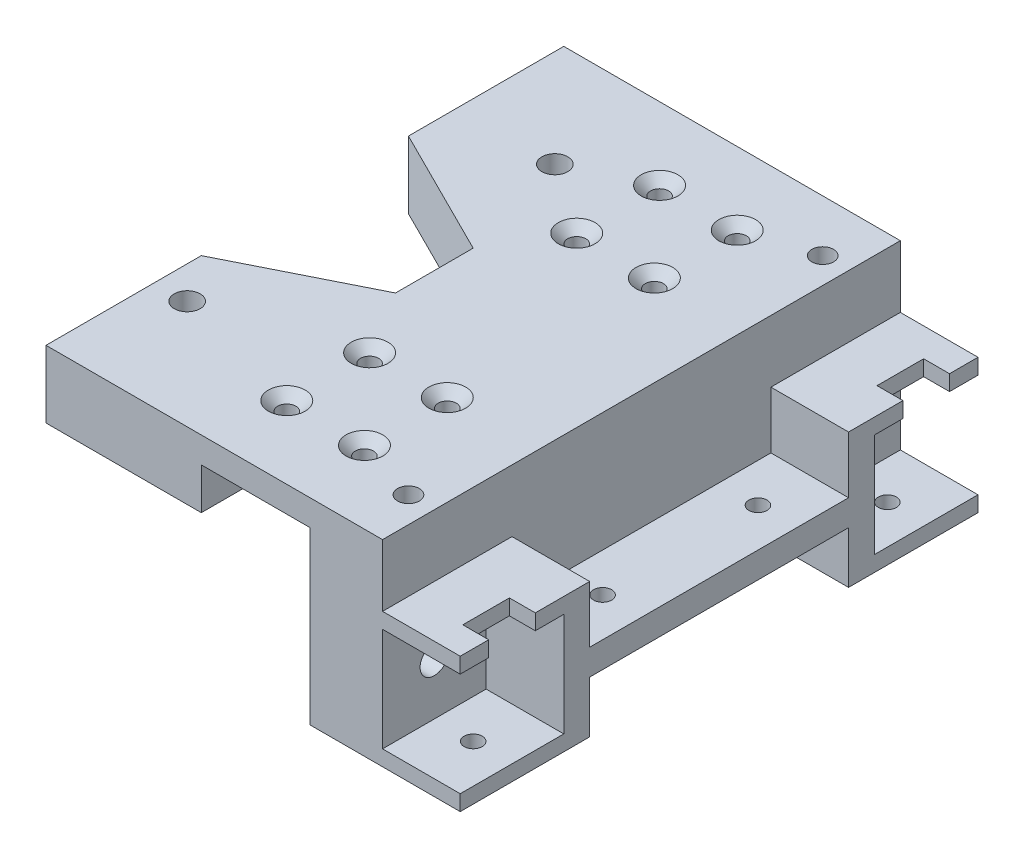
SolidWorks part; units mm, degrees
ref_plane "Front Plane" through (0, 0, 0) normal (0, 0, 1) x (1, 0, 0)
ref_plane "Top Plane" through (0, 0, 0) normal (0, 1, 0) x (1, 0, 0)
ref_plane "Right Plane" through (0, 0, 0) normal (1, 0, 0) x (0, 0, -1)
sketch "Sketch1" plane through (0, 0, 0) normal (0, 1, 0) x (1, 0, 0)
  line L0 (0, 50) -> (0, -50) construction
  line L1 (-10, 50) -> (10, 50)
  line L2 (-10, 50) -> (-10, -50)
  line L3 (-10, -50) -> (10, -50)
  line L4 (10, 50) -> (10, -50) construction
  line L5 (-10, 50) -> (10, -50) construction
  line L6 (-10, -50) -> (10, 50) construction
  line L7 (-7.5, 36) -> (7.5, 36) construction
  line L8 (-7.5, 36) -> (7.5, 20) construction
  line L9 (-10, 0) -> (10, 0) construction
  line L10 (-7.5, -36) -> (7.5, -20) construction
  line L11 (-7.5, -36) -> (7.5, -36) construction
  line L12 (-7.5, 20) -> (7.5, 20) construction
  line L13 (10, 50) -> (11, 50)
  line L14 (11, 50) -> (11, -50)
  line L15 (11, -50) -> (10, -50)
  circle A0 centre (-7.5, 36) radius 1.75
  circle A1 centre (7.5, 36) radius 1.75
  circle A2 centre (-7.5, 20) radius 1.75
  circle A3 centre (7.5, 20) radius 1.75
  circle A4 centre (7.5, -20) radius 1.75
  circle A5 centre (-7.5, -20) radius 1.75
  circle A6 centre (7.5, -36) radius 1.75
  circle A7 centre (-7.5, -36) radius 1.75
  point P0 (0, 0)
  point P16 (0, 36)
  dimension "D2" = 3.5
  dimension "D1" = 20
  dimension "D3" = 15
  dimension "D4" = 16
  dimension "D5" = 100
  dimension "D6" = 20
  dimension "D7" = 1
extrude "Boss-Extrude1" add sketch "Sketch1" along normal blind 5
sketch "Sketch2" plane through (11, 0, 0) normal (1, 0, 0) x (0, 0, -1)
  line L1 (-50, 5) -> (50, 5)
  line L2 (-50, 5) -> (-50, -33)
  line L3 (-50, -33) -> (50, -33)
  line L5 (50, 5) -> (50, -33)
  line L6 (50, 5) -> (50, 0) construction
  line L7 (-50, 5) -> (-50, 0) construction
  line L8 (-50, 5) -> (50, 5) construction
  dimension "D1" = 38
extrude "Boss-Extrude2" add sketch "Sketch2" along normal blind 14
sketch "Sketch3" plane through (25, 0, 0) normal (1, 0, 0) x (0, 0, -1)
  line L0 (0, 5) -> (0, -33) construction
  line L1 (-25, -18) -> (25, -18)
  line L2 (-25, -18) -> (-25, -23)
  line L3 (-25, -23) -> (25, -23)
  line L4 (25, -18) -> (25, -23)
  line L5 (50, 5) -> (-50, 5) construction
  line L6 (-50, -33) -> (50, -33) construction
  point P10 (0, -18)
  dimension "D1" = 5
  dimension "D2" = 50
  dimension "D3" = 10
extrude "Boss-Extrude3" add sketch "Sketch3" along normal blind 15
sketch "Sketch4" plane through (0, -18, 0) normal (0, 1, 0) x (1, 0, 0)
  line L0 (25, 0) -> (40, 0) construction
  line L1 (25, 25) -> (25, -25) construction
  line L2 (40, 25) -> (40, -25) construction
  line L3 (32.5, -15) -> (32.5, 15) construction
  circle A0 centre (32.5, 15) radius 1.75
  circle A1 centre (32.5, -15) radius 1.75
  point P8 (32.5, 0)
  dimension "D1" = 30
  dimension "D2" = 3.5
extrude "Cut-Extrude1" cut sketch "Sketch4" against normal through all
sketch "Sketch8" plane through (25, 0, 0) normal (1, 0, 0) x (0, 0, -1)
  line L0 (-50, 5) -> (-50, -33) construction
  line L1 (-50, -7) -> (-25, -7)
  line L2 (-50, -7) -> (-50, -10)
  line L3 (-50, -33) -> (-25, -33)
  line L4 (-25, -7) -> (-25, -33)
  line L5 (-50, -30) -> (-50, -33)
  line L6 (-50, -30) -> (-30, -30)
  line L8 (-50, -10) -> (-30, -10)
  line L9 (-30, -30) -> (-30, -10)
  line L10 (0, 20.9) -> (0, -20.9) construction
  line L11 (30, -30) -> (30, -10)
  line L12 (50, -10) -> (30, -10)
  line L13 (50, -30) -> (30, -30)
  line L14 (50, -30) -> (50, -33)
  line L15 (25, -7) -> (25, -33)
  line L16 (50, -33) -> (25, -33)
  line L17 (50, -7) -> (50, -10)
  line L18 (50, -7) -> (25, -7)
  line L19 (-50, -33) -> (50, -33) construction
  dimension "D1" = 3
  dimension "D2" = 5
  dimension "D3" = 3
  dimension "D4" = 20
  dimension "D5" = 20
extrude "Boss-Extrude6" add sketch "Sketch8" along normal blind 15
sketch "Sketch9" plane through (25, 0, 0) normal (1, 0, 0) x (0, 0, -1)
  line L0 (-50, -10) -> (-30, -30) construction
  line L1 (50, -10) -> (30, -30) construction
  circle A0 centre (-40, -20) radius 2.75
  circle A1 centre (40, -20) radius 2.75
  dimension "D1" = 5.5
extrude "Cut-Extrude3" cut sketch "Sketch9" against normal through all
sketch "Sketch10" plane through (11, 0, 0) normal (-1, 0, 0) x (0, 0, 1)
  circle A0 centre (-40, -20) radius 4.5
  circle A1 centre (40, -20) radius 4.5
  dimension "D1" = 9
extrude "Cut-Extrude4" cut sketch "Sketch10" against normal offset from surface (9 mm away) 5 up to face at (25, -20, 37.25)
sketch "Sketch11" plane through (0, -7, 0) normal (0, 1, 0) x (1, 0, 0)
  line L0 (40, -25) -> (40, -50) construction
  line L1 (40, -35.5) -> (35, -35.5)
  line L2 (40, -35.5) -> (40, -44.5)
  line L3 (40, -44.5) -> (35, -44.5)
  line L4 (35, -35.5) -> (35, -44.5)
  line L5 (35, -40) -> (40, -40) construction
  line L6 (40, -50) -> (25, -50) construction
  line L7 (-10, 0) -> (40, 0) construction
  line L8 (-10, 50) -> (-10, -50) construction
  line L9 (40, 25) -> (40, -25) construction
  line L10 (40, -35.5) -> (35, -35.5)
  line L11 (40, -44.5) -> (35, -44.5)
  line L12 (35, 40) -> (40, 40) construction
  line L13 (40, 44.5) -> (35, 44.5)
  line L14 (40, 35.5) -> (35, 35.5)
  line L15 (35, 35.5) -> (35, 44.5)
  line L16 (40, 44.5) -> (35, 44.5)
  line L17 (40, 35.5) -> (40, 44.5)
  line L18 (40, 35.5) -> (35, 35.5)
  line M7 (40, -50) -> (40, -25)
  dimension "D1" = 9
  dimension "D2" = 10
  dimension "D3" = 5
extrude "Cut-Extrude5" cut sketch "Sketch11" against normal up to next contours L1 L4 L3 M7 | L14 L17 L13 L15 region at (37.5, -7, 40) region at (37.5, -7, -40)
sketch "Sketch12" plane through (0, -30, 0) normal (0, 1, 0) x (1, 0, 0)
  line L0 (40, -40) -> (25, -40) construction
  line L1 (40, -30) -> (40, -50) construction
  line L2 (25, -25) -> (25, -50) construction
  line L3 (-20.9, 0) -> (20.9, 0) construction
  circle A0 centre (32.5, -40) radius 1.75
  circle A2 centre (32.5, 40) radius 1.75
  dimension "D1" = 3.5
extrude "Cut-Extrude6" cut sketch "Sketch12" against normal through all
sketch "Sketch13" plane through (-10, 0, 0) normal (-1, 0, 0) x (0, 0, 1)
  line L1 (-50, 5) -> (50, 5)
  line L2 (-50, 5) -> (-50, -8)
  line L3 (-50, -8) -> (50, -8)
  line L4 (50, 5) -> (50, -8)
  dimension "D1" = 13
extrude "Boss-Extrude7" add sketch "Sketch13" along normal blind 30
sketch "Sketch14" plane through (0, 5, 0) normal (0, 1, 0) x (1, 0, 0)
  line L0 (-40, -50) -> (25, -50) construction
  line L1 (-10.5, -50) -> (10.5, -50) construction
  line L2 (-10.5, -50) -> (-10.5, 50) construction
  line L3 (-10.5, 50) -> (10.5, 50) construction
  line L4 (10.5, -50) -> (10.5, 50) construction
  line L5 (25, 50) -> (-40, 50) construction
  line L6 (-27.23, 29.42) -> (-27.23, -29) construction
  line L12 (-33.73, -35.5) -> (40, -35.5) construction
  line L18 (-21.15, 35.5) -> (40, 35.5) construction
  circle A0 centre (-21.15, 29.42) radius 2.5
  circle A1 centre (-33.73, -29) radius 2.5
  circle A2 centre (-33.73, -29) radius 6.5 construction
  circle A3 centre (-21.15, 29.42) radius 6.08 construction
  point P14 (0, 50)
  point P20 (40, 35.5)
  dimension "D1" = 5
  dimension "D2" = 5
  dimension "D4" = 21
  dimension "D5" = 13
  dimension "D6" = 12.16
  dimension "D3" = 21.15
extrude "Cut-Extrude7" cut sketch "Sketch14" against normal through all
sketch "Sketch15" plane through (0, -8, 0) normal (0, -1, 0) x (1, 0, 0)
  line L0 (-40, -50) -> (-40, 50) construction
  line L1 (-29.73, 26.6906) -> (-29.73, 31.3094)
  line L2 (-29.73, 31.3094) -> (-33.73, 33.6188)
  line L3 (-33.73, 33.6188) -> (-37.73, 31.3094)
  line L4 (-37.73, 31.3094) -> (-37.73, 26.6906)
  line L5 (-37.73, 26.6906) -> (-33.73, 24.3812)
  line L6 (-33.73, 24.3812) -> (-29.73, 26.6906)
  line L7 (-25.15, -31.7294) -> (-21.15, -34.0388)
  line L8 (-21.15, -34.0388) -> (-17.15, -31.7294)
  line L9 (-17.15, -31.7294) -> (-17.15, -27.1106)
  line L10 (-17.15, -27.1106) -> (-21.15, -24.8012)
  line L11 (-21.15, -24.8012) -> (-25.15, -27.1106)
  line L12 (-25.15, -27.1106) -> (-25.15, -31.7294)
  circle A0 centre (-33.73, 29) radius 4 construction
  circle A1 centre (-21.15, -29.42) radius 4 construction
  dimension "D1" = 8
extrude "Cut-Extrude8" cut sketch "Sketch15" against normal blind 4
sketch "Sketch16" plane through (0, 5, 0) normal (0, 1, 0) x (1, 0, 0)
  line L0 (20, 40) -> (40, 40) construction
  line L1 (40, 50) -> (40, 30) construction
  line L2 (20, -40) -> (40, -40) construction
  line L3 (40, -30) -> (40, -50) construction
  circle A0 centre (20, 40) radius 2.1
  circle A1 centre (20, -40) radius 2.1
  point P8 (38.3273, -39.0525)
  point P9 (40, -40)
  dimension "D1" = 4.2
  dimension "D2" = 4.2
  dimension "D3" = 20
extrude "Cut-Extrude9" cut sketch "Sketch16" against normal blind 4
chamfer "Chamfer1" distance 1.8 angle 45 8 edges at (-7.5, 5, -34.25) (7.5, 5, -34.25) (-7.5, 5, -18.25) (7.5, 5, -18.25) (-7.5, 5, 18.25) (7.5, 5, 18.25) (-7.5, 5, 34.25) (7.5, 5, 34.25)
sketch "Sketch17" plane through (0, 5, 0) normal (0, 1, 0) x (1, 0, 0)
  line L0 (-40, 20) -> (-15, 7.5)
  line L1 (-40, -50) -> (-40, 50) construction
  line L2 (-15, 7.5) -> (-15, -7.5)
  line L3 (-15, -7.5) -> (-40, -20)
  line L4 (-40, -20) -> (-40, 20)
  point P6 (-15, 0)
  point P7 (-15.7369, -7.0857)
  point P9 (-40, -21.3396)
  dimension "D1" = 15
  dimension "D2" = 40
  dimension "D3" = 15
extrude "Cut-Extrude10" cut sketch "Sketch17" against normal through all
